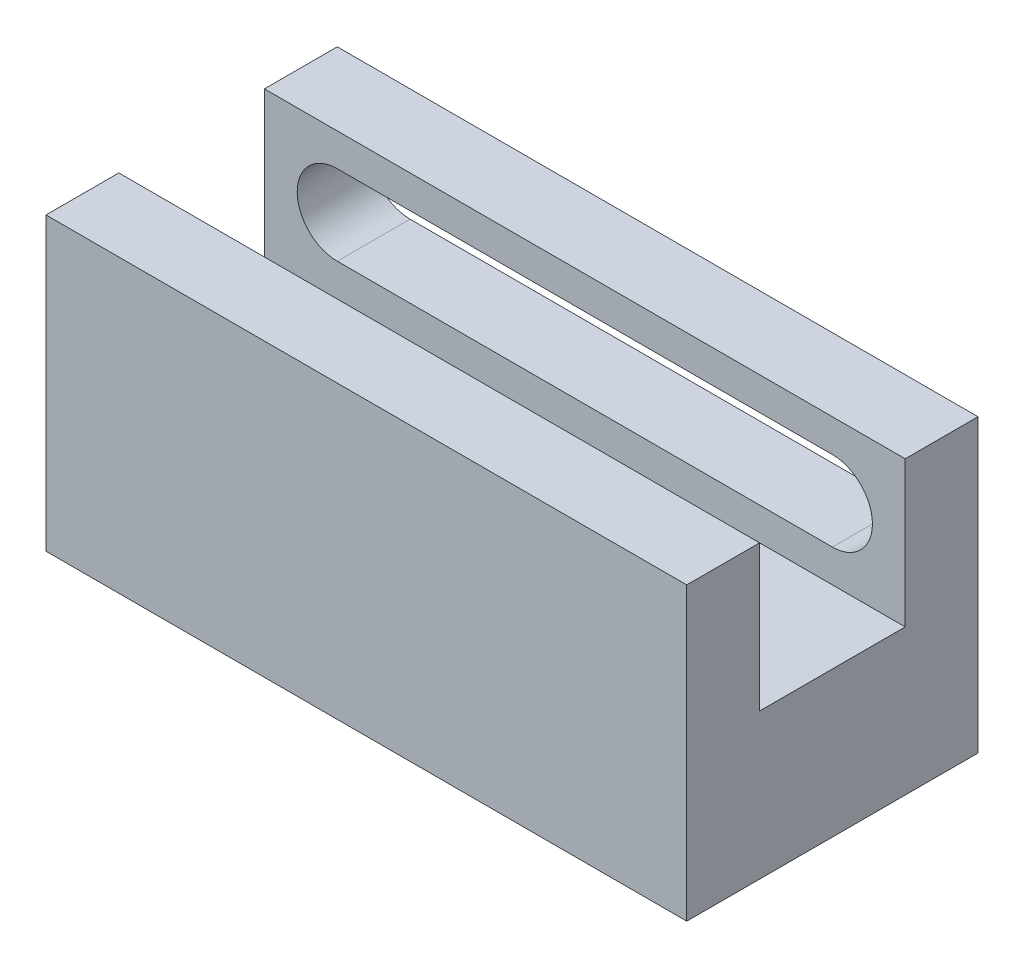
SolidWorks part; units mm, degrees
ref_plane "Front Plane" through (0, 0, 0) normal (0, 0, 1) x (1, 0, 0)
ref_plane "Top Plane" through (0, 0, 0) normal (0, 1, 0) x (1, 0, 0)
ref_plane "Right Plane" through (0, 0, 0) normal (1, 0, 0) x (0, 0, -1)
sketch "Sketch1" plane through (0, 0, 0) normal (0, 1, 0) x (1, 0, 0)
  line L1 (0, 20) -> (44, 20)
  line L2 (0, 20) -> (0, 0)
  line L3 (0, 0) -> (44, 0)
  line L4 (44, 20) -> (44, 0)
  circle A0 centre (22, 10) radius 2.55
  point P8 (22, 20)
  point P10 (44, 10)
  dimension "D3" = 5.1
  dimension "D1" = 44
  dimension "D2" = 20
extrude "Boss-Extrude1" add sketch "Sketch1" along normal blind 7.5
sketch "Sketch2" plane through (0, 7.5, 0) normal (0, 1, 0) x (1, 0, 0)
  line L0 (44, 0) -> (44, 20) construction
  line L1 (44, 0) -> (0, 0)
  line L2 (44, 0) -> (44, 20)
  line L3 (44, 20) -> (0, 20)
  line L4 (0, 0) -> (0, 20)
  line L5 (0, 20) -> (0, 0) construction
  line L6 (44, 20) -> (0, 20) construction
  line L7 (0, 0) -> (44, 0) construction
extrude "Boss-Extrude2" add sketch "Sketch2" along normal blind 2.5
sketch "Sketch3" plane through (0, 10, 0) normal (0, 1, 0) x (1, 0, 0)
  line L0 (0, 0) -> (44, 0) construction
  line L1 (0, 5) -> (44, 5)
  line L2 (0, 5) -> (0, 0)
  line L3 (0, 0) -> (44, 0)
  line L4 (44, 5) -> (44, 0)
  line L5 (44, 0) -> (44, 20) construction
  line L6 (0, 20) -> (0, 0) construction
  line L7 (44, 20) -> (0, 20) construction
  line L8 (44, 15) -> (0, 15)
  line L9 (44, 15) -> (44, 20)
  line L10 (44, 20) -> (0, 20)
  line L11 (0, 15) -> (0, 20)
  dimension "D1" = 5
  dimension "D2" = 5
extrude "Boss-Extrude3" add sketch "Sketch3" along normal blind 10
sketch "Sketch4" plane through (0, 0, -20) normal (0, 0, -1) x (-1, 0, 0)
  line L0 (-44, 20) -> (-44, 0) construction
  line L1 (-39, 17.75) -> (-5, 17.75)
  line L2 (-39, 17.75) -> (-39, 12.25)
  line L3 (-39, 12.25) -> (-5, 12.25)
  line L4 (-5, 17.75) -> (-5, 12.25)
  line L5 (0, 20) -> (0, 0) construction
  line L6 (-44, 20) -> (0, 20) construction
  circle A0 centre (-39, 15) radius 2.75
  circle A1 centre (-5, 15) radius 2.75
  point P6 (-5, 15)
  point P12 (-39, 15)
  dimension "D3" = 5.5
  dimension "D1" = 5
  dimension "D2" = 5
  dimension "D4" = 5
extrude "Cut-Extrude1" cut sketch "Sketch4" against normal blind 5 and the other way through all contours A1 L1 A0 L3 | L2 A0 | L2 A0 | L4 A1 | L4 A1 region at (37.8329, 15, -20) region at (22, 15, -20) region at (40.1671, 15, -20) region at (3.8329, 15, -20) region at (6.1671, 15, -20)
